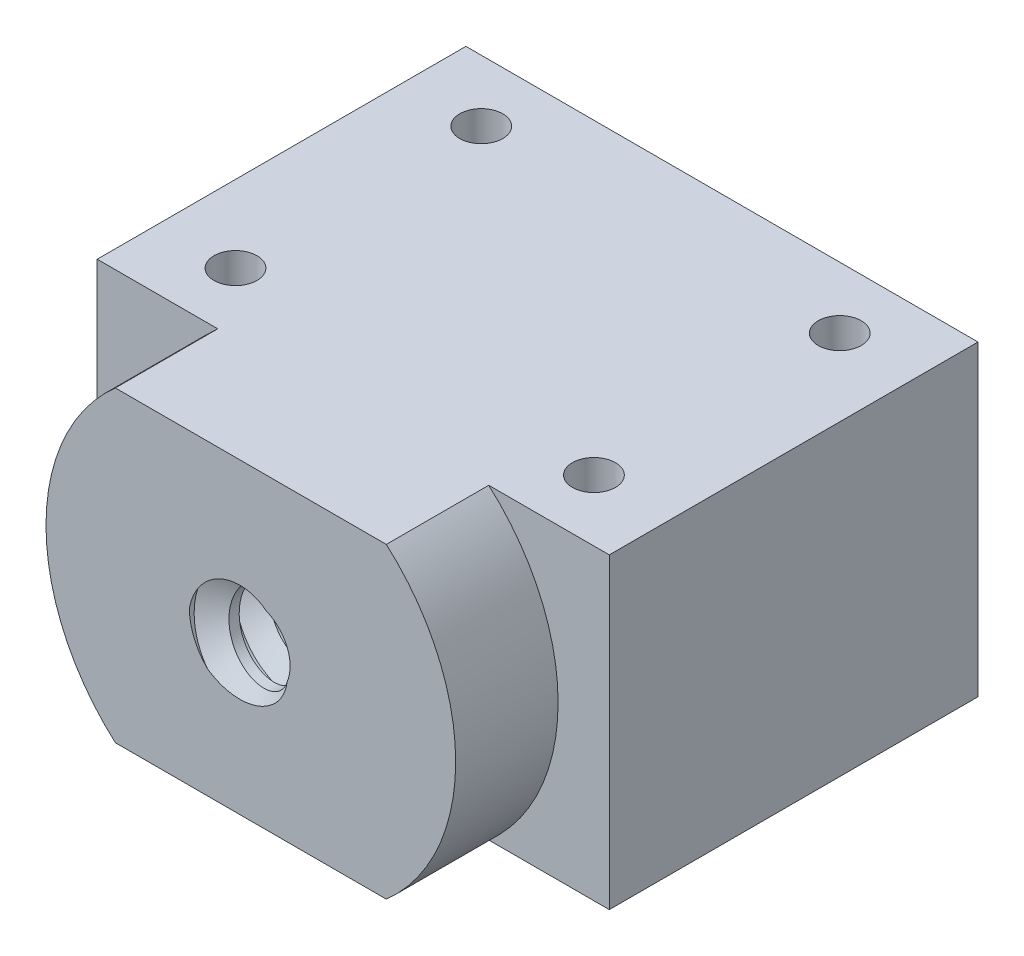
SolidWorks part; units mm, degrees
ref_plane "Front Plane" through (0, 0, 0) normal (0, 0, 1) x (1, 0, 0)
ref_plane "Top Plane" through (0, 0, 0) normal (0, 1, 0) x (1, 0, 0)
ref_plane "Right Plane" through (0, 0, 0) normal (1, 0, 0) x (0, 0, -1)
sketch "Sketch1" plane through (0, 0, 0) normal (0, 0, 1) x (1, 0, 0)
  line L0 (0, 15) -> (0, -15) construction
  line L1 (-25, 15) -> (25, 15)
  line L2 (-25, 15) -> (-25, -15)
  line L3 (-25, -15) -> (25, -15)
  line L4 (25, 15) -> (25, -15)
  line L5 (-25, 15) -> (25, -15) construction
  line L6 (-25, -15) -> (25, 15) construction
  circle A0 centre (0, 0) radius 6
  point P0 (0, 0)
  dimension "D3" = 12
  dimension "D1" = 30
  dimension "D2" = 50
extrude "Boss-Extrude1" add sketch "Sketch1" along normal blind 36
hole_wizard "M5 Tapped Hole1" [suppressed] positions "Sketch2" profile "Sketch3" tap size "M5" standard "ISO"
sketch "Sketch2" plane through (0, 0, 36) normal (0, 0, 1) x (1, 0, 0)
  line L0 (-11.3137, 11.3137) -> (0, 0) construction
  line L2 (0, 0) -> (0, 15) construction
  line L3 (25, 15) -> (-25, 15) construction
  point P0 (-11.3137, 11.3137)
  point P21 (11.3137, 11.3137)
  point P22 (16, 0)
  point P23 (11.3137, -11.3137)
  point P25 (-11.3137, -11.3137)
  point P26 (-16, 0)
  point P28 (-32.0747, 52.2798)
  dimension "D1" = 16
  dimension "D2" = 45
cosmetic thread "Hole Thread1" [suppressed] parameters "D1"=10, "D2"=5
cosmetic thread "Hole Thread2" [suppressed] parameters "D1"=10, "D2"=5
cosmetic thread "Hole Thread3" [suppressed] parameters "D1"=10, "D2"=5
cosmetic thread "Hole Thread4" [suppressed] parameters "D1"=10, "D2"=5
cosmetic thread "Hole Thread5" [suppressed] parameters "D1"=10, "D2"=5
cosmetic thread "Hole Thread6" [suppressed] parameters "D1"=10, "D2"=5
sketch "Sketch3" plane through (-11.3137, 11.3137, 36) normal (1, 0, 0) x (0, -1, 0)
  line L0 (0, 0) -> (0, 11.2618)
  line L1 (0, 11.2618) -> (2.1, 10)
  line L2 (2.1, 10) -> (2.1, 0)
  line L5 (2.1, 0) -> (0, 0)
  line L10 (0, 11.2618) -> (-2.1, 10) construction
  line L11 (0, -6.35) -> (0, 107.95) construction
  dimension "Tap Drill Dia." = 4.2
  dimension "Tap Drill Depth" = 10
  dimension "Drill Angle" = 118
hole_wizard "M5 Tapped Hole2" positions "Sketch4" profile "Sketch5" tap size "M5" standard "ISO"
sketch "Sketch4" plane through (0, 15, 0) normal (0, 1, 0) x (1, 0, 0)
  line L0 (0, 0) -> (0, -36) construction
  line L1 (25, 0) -> (-25, 0) construction
  line L2 (25, -36) -> (-25, -36) construction
  line L4 (-25, -18) -> (25, -18) construction
  line L5 (-25, -36) -> (-25, 0) construction
  line L6 (25, -36) -> (25, 0) construction
  point P0 (-17.5, -6)
  point P10 (17.5, -6)
  point P11 (17.5, -30)
  point P12 (-17.5, -30)
  dimension "D1" = 2
  dimension "D2" = 2
cosmetic thread "Hole Thread7" parameters "D1"=10, "D2"=5
cosmetic thread "Hole Thread8" parameters "D1"=10, "D2"=5
cosmetic thread "Hole Thread9" parameters "D1"=10, "D2"=5
cosmetic thread "Hole Thread10" parameters "D1"=10, "D2"=5
sketch "Sketch5" plane through (-17.5, 15, 6) normal (1, 0, 0) x (0, 0, 1)
  line L0 (0, 0) -> (0, 11.2618)
  line L1 (0, 11.2618) -> (2.1, 10)
  line L2 (2.1, 10) -> (2.1, 0)
  line L5 (2.1, 0) -> (0, 0)
  line L10 (0, 11.2618) -> (-2.1, 10) construction
  line L11 (0, -6.35) -> (0, 107.95) construction
  dimension "Tap Drill Dia." = 4.2
  dimension "Tap Drill Depth" = 10
  dimension "Drill Angle" = 118
sketch "Sketch6" plane through (0, 0, 36) normal (0, 0, 1) x (1, 0, 0)
  line L0 (-13.2288, -15) -> (13.2288, -15)
  line L1 (-13.2288, 15) -> (13.2288, 15)
  arc A0 (-13.2288, 15) -> (-13.2288, -15) centre (0, 0) ccw
  arc A1 (13.2288, -15) -> (13.2288, 15) centre (0, 0) ccw
  circle A2 centre (0, 0) radius 6
  dimension "D1" = 20
  dimension "D2" = 12
extrude "Boss-Extrude3" add sketch "Sketch6" along normal blind 10
sketch "Sketch8" plane through (0, 0, 0) normal (0, 0, -1) x (-1, 0, 0)
  circle A0 centre (0, 0) radius 11
  dimension "D1" = 22
extrude "Cut-Extrude1" cut sketch "Sketch8" against normal blind 6
thread "Thread1" pitch 4 method extrude trim with start face yes trim with end face yes profile "Thread Profile2" start angle 0, offset 6, length 0, pitch 4, diameter 12
ref_plane "Plane2" through (6, 0, 0) normal (0, -1, 0) x (1, 0, 0)
sketch "Thread Profile2" plane through (6, 0, 0) normal (0, -1, 0) x (1, 0, 0)
  line L0 (0, 0) -> (0, 4) construction
  line L11 (0, 0) -> (0, 3.5)
  line L12 (0, 3.5) -> (-2.1651, 2.25)
  line L13 (-2.1651, 2.25) -> (-2.1651, 1.25)
  line L15 (-2.1651, 1.25) -> (0, 0)
  line L17 (-2.1651, 1.75) -> (0, 1.75) construction
  point P2 (0, 0)
  dimension "Pitch" = 4
  dimension "Profile_Angle" = 60
  dimension "Profile_Land" = 1
  dimension "Profile_Height" = 2.1651
